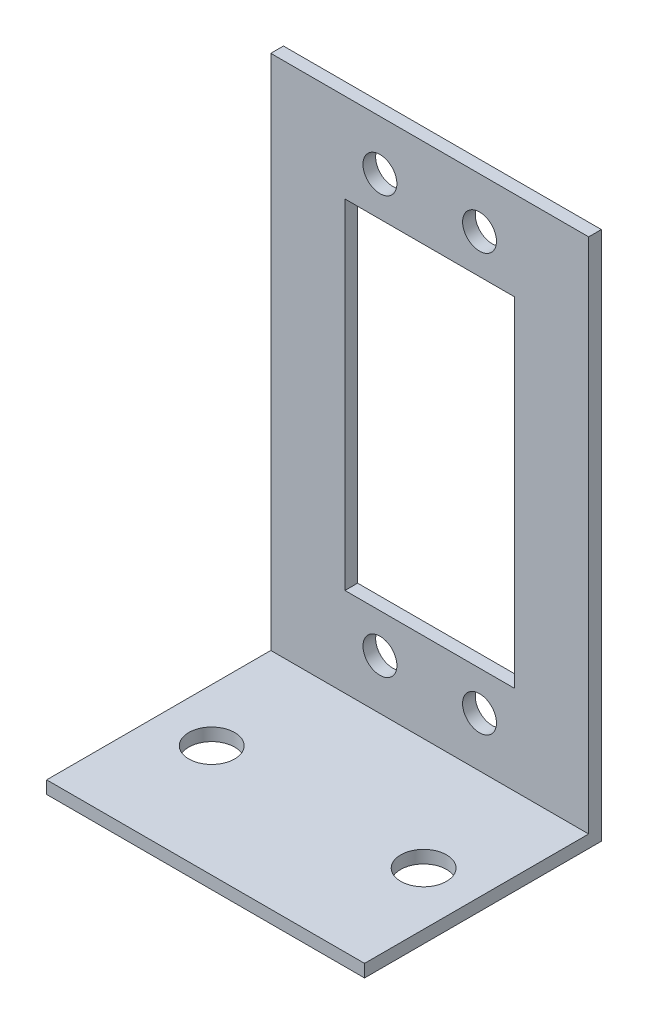
SolidWorks part; units mm, degrees
material "AISI 1020"
ref_plane "Front Plane" through (0, 0, 0) normal (0, 0, 1) x (1, 0, 0)
ref_plane "Top Plane" through (0, 0, 0) normal (0, 1, 0) x (1, 0, 0)
ref_plane "Right Plane" through (0, 0, 0) normal (1, 0, 0) x (0, 0, -1)
sketch "Sketch1" plane through (0, 0, 0) normal (1, 0, 0) x (0, 0, -1)
  line L0 (0, 0) -> (28.3806, 0)
  line L1 (28.3806, 0) -> (28.3806, 63.5)
  line L2 (28.3806, 63.5) -> (26.8617, 63.5)
  line L3 (26.8617, 63.5) -> (26.8617, 1.5189)
  line L4 (26.8617, 1.5189) -> (0, 1.5189)
  line L5 (0, 1.5189) -> (0, 0)
  dimension "D1" = 1.5189
  dimension "D2" = 63.5
extrude "Boss-Extrude1" add sketch "Sketch1" along normal mid plane 38.1
hole_wizard "M5 Clearance Hole1" positions "Sketch3" profile "Sketch4" hole size "M5" standard "ANSI Metric" end condition through all
sketch "Sketch3" plane through (0, 1.5189, 0) normal (0, 1, 0) x (1, 0, 0)
  line L0 (-12.7, 13.4308) -> (12.7, 13.4308) construction
  line L2 (-19.05, 26.8617) -> (-19.05, 0) construction
  point P0 (-12.7, 13.4308)
  point P2 (12.7, 13.4308)
  point P9 (0, 13.4308)
  point P14 (-19.05, 13.4308)
  dimension "D1" = 25.4
sketch "Sketch4" plane through (-12.7, 1.5189, -13.4308) normal (1, 0, 0) x (0, 0, 1)
  line L0 (0, 0) -> (0, 1.5189)
  line L1 (0, 1.5189) -> (2.75, 1.5189)
  line L2 (2.75, 1.5189) -> (2.75, 0)
  line L5 (2.75, 0) -> (0, 0)
  line L11 (0, -6.35) -> (0, 107.95) construction
  dimension "Thru Hole Dia." = 5.5
  dimension "Thru Hole Depth" = 1.5189
sketch "Sketch5" plane through (0, 0, -26.8617) normal (0, 0, 1) x (1, 0, 0)
  line L0 (19.05, 63.5) -> (-19.05, 63.5) construction
  line L1 (-10.16, 52.8295) -> (10.16, 52.8295)
  line L2 (-10.16, 52.8295) -> (-10.16, 12.1895)
  line L3 (-10.16, 12.1895) -> (10.16, 12.1895)
  line L4 (10.16, 52.8295) -> (10.16, 12.1895)
  line L5 (-10.16, 52.8295) -> (10.16, 12.1895) construction
  line L6 (-10.16, 12.1895) -> (10.16, 52.8295) construction
  line L7 (19.05, 63.5) -> (19.05, 1.5189) construction
  point P0 (0, 32.5095)
  point P8 (0, 63.5)
  point P13 (19.05, 32.5095)
  dimension "D1" = 40.64
  dimension "D2" = 20.32
extrude "Cut-Extrude1" cut sketch "Sketch5" against normal up to next
sketch "Sketch6" plane through (0, 0, -26.8617) normal (0, 0, 1) x (1, 0, 0)
  line L0 (-5.969, 57.5095) -> (5.969, 57.5095) construction
  line L1 (-10.16, 32.5095) -> (10.16, 32.5095) construction
  line L2 (-10.16, 52.8295) -> (-10.16, 12.1895) construction
  line L3 (10.16, 12.1895) -> (10.16, 52.8295) construction
  circle A0 centre (-5.969, 57.5095) radius 2.032
  circle A1 centre (5.969, 57.5095) radius 2.032
  circle A2 centre (-5.969, 7.5095) radius 2.032
  circle A3 centre (5.969, 7.5095) radius 2.032
  point P4 (0, 57.5095)
  dimension "D2" = 4.064
  dimension "D1" = 11.938
  dimension "D3" = 50
extrude "Cut-Extrude2" cut sketch "Sketch6" against normal up to next
